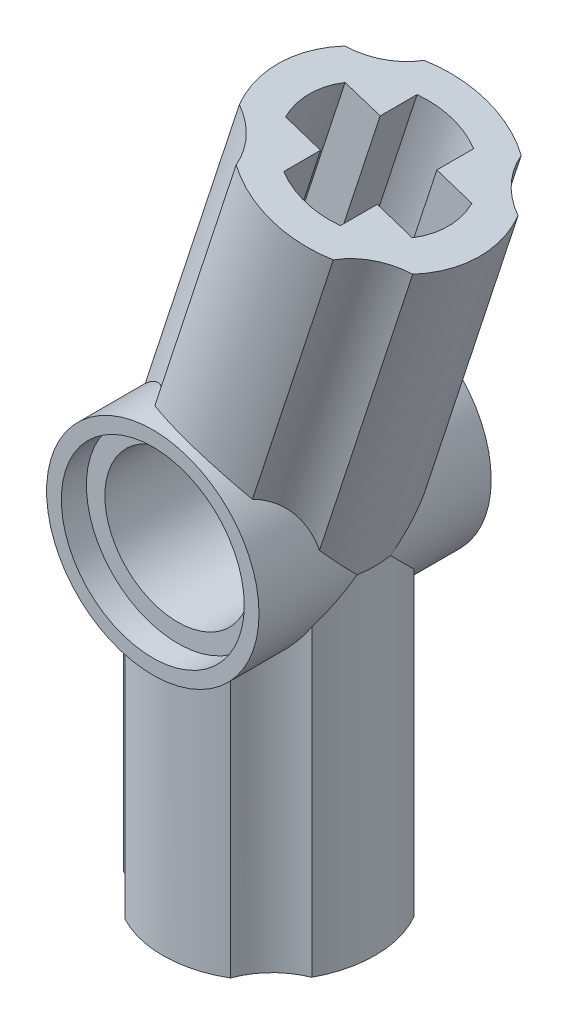
SolidWorks part; units mm, degrees
ref_plane "Front Plane" through (0, 0, 0) normal (0, 0, 1) x (1, 0, 0)
ref_plane "Top Plane" through (0, 0, 0) normal (0, 1, 0) x (1, 0, 0)
ref_plane "Right Plane" through (0, 0, 0) normal (1, 0, 0) x (0, 0, -1)
sketch "Croquis1" plane through (0, 0, 0) normal (0, 0, 1) x (1, 0, 0)
  circle A0 centre (0, 0) radius 3.1
  circle A1 centre (0, 0) radius 3.6
  circle A2 centre (0, 0) radius 2.475
  dimension "D1" = 4.95
  dimension "D2" = 6.2
  dimension "D3" = 7.2
extrude "Saliente-Extruir1" add sketch "Croquis1" along normal blind 7.87 contours A1 A0 region at (-3.4982, 0, 0)
extrude "Saliente-Extruir2" add sketch "Croquis1<3>" along normal offset from surface (6.17 mm away) 0.85 from offset 0.85 contours A0 A2 region at (-3.0123, 0, 0) up to face at (3.1, 0, 7.87)
sketch "Croquis1<3>" plane through (0, 0, 0) normal (0, 0, 1) x (1, 0, 0) same geometry as "Croquis1"
ref_plane "Plano1" through (0, -4, 0) normal (0, 1, 0) x (1, 0, 0)
sketch "Croquis2" plane through (0, -4, 0) normal (0, 1, 0) x (1, 0, 0)
  line L0 (-1.01, -6.1945) -> (-1.01, -4.945)
  line L1 (1.01, -6.1945) -> (1.01, -4.945)
  line L2 (-2.2595, -2.925) -> (-1.01, -2.925)
  line L3 (2.2595, -4.945) -> (1.01, -4.945)
  line L4 (-1.01, -4.945) -> (-2.2595, -4.945)
  line L5 (1.01, -2.925) -> (1.01, -1.6755)
  line L6 (-1.01, -2.925) -> (-1.01, -1.6755)
  line L7 (1.01, -2.925) -> (2.2595, -2.925)
  arc A0 (-1.01, -6.1945) -> (1.01, -6.1945) centre (0, -3.935) ccw
  arc A1 (-1.7125, -7.1016) -> (1.8067, -7.0488) centre (0, -3.935) ccw
  arc A2 (-1.7125, -7.1016) -> (-3.1138, -5.7417) centre (-3.94, -7.995) ccw
  arc A3 (-3.1666, -2.2225) -> (-1.8067, -0.8212) centre (-4.06, 0.005) ccw
  arc A4 (1.7125, -0.7684) -> (3.1138, -2.1283) centre (3.94, 0.125) ccw
  arc A5 (3.1666, -5.6475) -> (1.8067, -7.0488) centre (4.06, -7.875) ccw
  arc A6 (3.1666, -5.6475) -> (3.1138, -2.1283) centre (0, -3.935) ccw
  arc A7 (1.7125, -0.7684) -> (-1.8067, -0.8212) centre (0, -3.935) ccw
  arc A8 (-3.1666, -2.2225) -> (-3.1138, -5.7417) centre (0, -3.935) ccw
  arc A9 (2.2595, -4.945) -> (2.2595, -2.925) centre (0, -3.935) ccw
  arc A10 (1.01, -1.6755) -> (-1.01, -1.6755) centre (0, -3.935) ccw
  arc A11 (-2.2595, -2.925) -> (-2.2595, -4.945) centre (0, -3.935) ccw
  dimension "D2" = 4.95
  dimension "D3" = 7.2
  dimension "D4" = 4.8
  dimension "D1" = 3.935
  dimension "D5" = 3.94
  dimension "D6" = 4.06
  dimension "D8" = 2.02
  dimension "D9" = 1.01
  dimension "D10" = 2.02
  dimension "D11" = 1.01
  dimension "D7" = 4
extrude "Saliente-Extruir3" add sketch "Croquis2" along normal up to surface (0.8334 mm away) contours A3 A8 A2 A1 A5 A6 A4 A7 A11 L2 L6 A10 L5 L7 A9 L3 L1 A0 L0 L4 up to face at (3.6, 0, 7.87)
extrude "Saliente-Extruir4" add sketch "Croquis2<3>" against normal blind 8 contours A3 A8 A2 A1 A5 A6 A4 A7 A11 L2 L6 A10 L5 L7 A9 L3 L1 A0 L0 L4 region at (-2.1977, -4, 6.1996)
sketch "Croquis2<3>" plane through (0, -4, 0) normal (0, 1, 0) x (1, 0, 0) same geometry as "Croquis2"
sketch "Croquis5" plane through (0, 0, 0) normal (1, 0, 0) x (0, 0, -1)
  line L0 (0, 0) -> (-7.87, 0) construction
  line L1 (-7.87, 3.6) -> (-7.87, -3.6) construction
ref_plane "Plano3" through (0, 0, 0) normal (-0.3102, -0.9507, 0) x (0, 0, 1)
ref_plane "Plano4" through (1.2407, 3.8027, 0) normal (-0.3102, -0.9507, 0) x (0, 0, 1)
sketch "Croquis7" plane through (1.2407, 3.8027, 0) normal (-0.3102, -0.9507, 0) x (0, 0, 1)
  line L0 (2.925, -2.2595) -> (2.925, -1.01)
  line L1 (4.945, -2.2595) -> (4.945, -1.01)
  line L2 (1.6755, 1.01) -> (2.925, 1.01)
  line L3 (6.1945, -1.01) -> (4.945, -1.01)
  line L4 (2.925, -1.01) -> (1.6755, -1.01)
  line L5 (4.945, 1.01) -> (4.945, 2.2595)
  line L6 (2.925, 1.01) -> (2.925, 2.2595)
  line L7 (4.945, 1.01) -> (6.1945, 1.01)
  line L8 (7.87, -3.6) -> (7.87, 3.6) construction
  arc A0 (2.925, -2.2595) -> (4.945, -2.2595) centre (3.935, 0) ccw
  arc A1 (2.2225, -3.1666) -> (5.7417, -3.1138) centre (3.935, 0) ccw
  arc A2 (2.2225, -3.1666) -> (0.8212, -1.8067) centre (-0.005, -4.06) ccw
  arc A4 (5.6475, 3.1666) -> (7.0488, 1.8067) centre (7.875, 4.06) ccw
  arc A6 (7.1016, -1.7125) -> (7.0488, 1.8067) centre (3.935, 0) ccw
  arc A7 (5.6475, 3.1666) -> (2.1283, 3.1138) centre (3.935, 0) ccw
  arc A8 (0.7684, 1.7125) -> (0.8212, -1.8067) centre (3.935, 0) ccw
  arc A9 (6.1945, -1.01) -> (6.1945, 1.01) centre (3.935, 0) ccw
  arc A10 (4.945, 2.2595) -> (2.925, 2.2595) centre (3.935, 0) ccw
  arc A11 (1.6755, 1.01) -> (1.6755, -1.01) centre (3.935, 0) ccw
  arc A12 (7.1016, -1.7125) -> (5.7417, -3.1138) centre (7.995, -3.94) ccw
  arc A13 (2.2225, -3.1666) -> (0.8212, -1.8067) centre (-0.005, -4.06) ccw
  arc A14 (0.7684, 1.7125) -> (2.1283, 3.1138) centre (-0.125, 3.94) ccw
  dimension "D1" = 4.95
  dimension "D2" = 7.2
  dimension "D3" = 4.8
  dimension "D13" = 2.4
  dimension "D4" = 3.94
  dimension "D5" = 4.06
  dimension "D6" = 2.02
  dimension "D7" = 1.01
  dimension "D8" = 2.02
  dimension "D9" = 1.01
  dimension "D10" = 3.935
  dimension "D11" = 3.94
  dimension "D12" = 4.06
  dimension "D14" = 4
extrude "Saliente-Extruir5" add sketch "Croquis7" along normal up to surface (0.8334 mm away) contours A12 A1 A2 A8 A14 A7 A4 A6 up to face at (0, -2.0794, 3.935)
extrude "Saliente-Extruir6" add sketch "Croquis7<3>" against normal blind 8 contours A14 A8 A2 A1 A12 A6 A4 A7 A11 L2 L6 A10 L5 L7 A9 L3 L1 A0 L0 L4 region at (3.3936, 3.1003, 1.7373)
sketch "Croquis7<3>" plane through (1.2407, 3.8027, 0) normal (-0.3102, -0.9507, 0) x (0, 0, 1) same geometry as "Croquis7"
equation "\"D9@Croquis2\"=\"D8@Croquis2\"/2"
equation "\"D11@Croquis2\"=\"D10@Croquis2\"/2"
equation "\"angle\"= 163"
